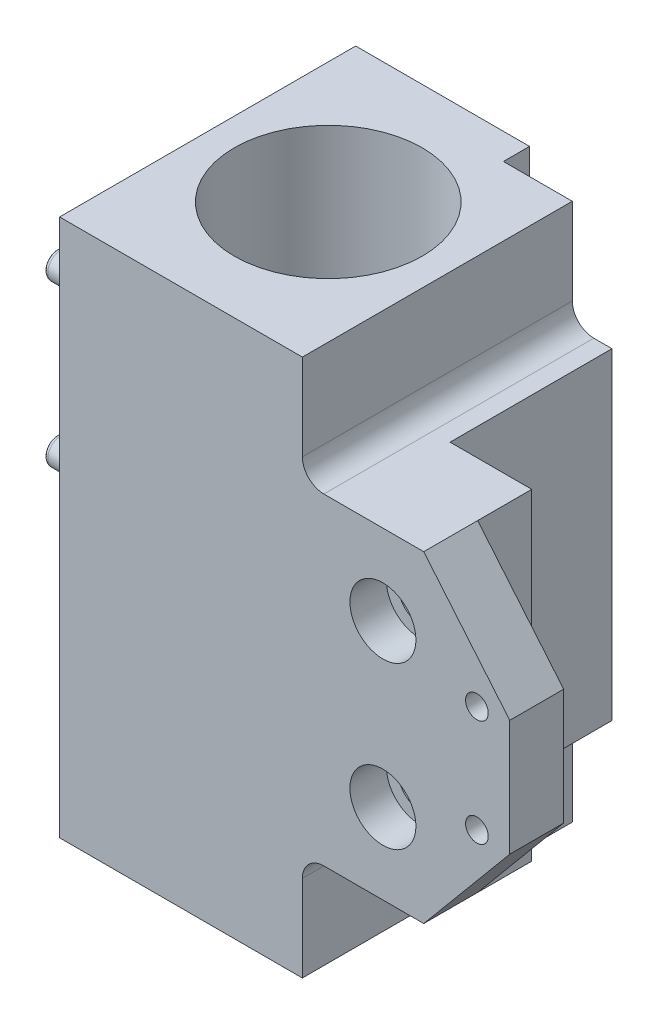
SolidWorks part; units mm, degrees
material "1060 Alloy"
ref_plane "Front Plane" through (0, 0, 0) normal (0, 0, 1) x (1, 0, 0)
ref_plane "Top Plane" through (0, 0, 0) normal (0, 1, 0) x (1, 0, 0)
ref_plane "Right Plane" through (0, 0, 0) normal (1, 0, 0) x (0, 0, -1)
sketch "Sketch1" plane through (0, 0, 0) normal (0, 1, 0) x (1, 0, 0)
  line L0 (-14.34, 17.58) -> (-14.34, -17.4)
  line L1 (-14.34, -17.4) -> (38.84, -17.4)
  line L2 (38.84, -17.4) -> (38.84, -11.03)
  line L3 (38.84, -11.03) -> (28.68, -11.03)
  line L4 (28.68, -11.03) -> (28.68, -4.64)
  line L5 (28.68, -4.64) -> (19.03, -4.64)
  line L6 (14.34, -4.64) -> (14.34, 14.49) construction
  line L7 (14.34, 14.49) -> (6.2, 14.49)
  line L8 (6.2, 14.49) -> (6.2, 17.58)
  line L9 (6.2, 17.58) -> (-14.34, 17.58)
  line L10 (0, 0) -> (0, 51.3699) construction
  line L11 (0, -11.1) -> (-14.34, -11.1) construction
  line L12 (14.34, 14.49) -> (19.03, 14.49)
  line L13 (19.03, 14.49) -> (19.03, -4.64)
  line L14 (14.34, -4.64) -> (19.03, -4.64) construction
  circle A0 centre (0, 0) radius 11.1
  dimension "D1" = 22.2
  dimension "D2" = 28.68
  dimension "D3" = 20.54
  dimension "D4" = 53.18
  dimension "D5" = 43.02
  dimension "D6" = 6.3
  dimension "D7" = 34.98
  dimension "D8" = 31.89
  dimension "D9" = 12.76
  dimension "D10" = 6.37
  dimension "D11" = 33.37
extrude "Boss-Extrude1" add sketch "Sketch1" along normal blind 31.765 and the other way blind 31.765
sketch "Sketch2" plane through (-14.34, 0, 0) normal (-1, 0, 0) x (0, 0, 1)
  line L0 (0, 0) -> (18.9221, 0) construction
  line L1 (-6.365, -19.06) -> (6.365, -19.06)
  line L2 (-6.365, -19.06) -> (-6.365, 19.06)
  line L3 (-6.365, 19.06) -> (6.365, 19.06)
  line L4 (6.365, -19.06) -> (6.365, 19.06)
  line L5 (0, 0) -> (0, -42.4085) construction
  dimension "D1" = 38.12
  dimension "D2" = 12.73
extrude "Boss-Extrude2" add sketch "Sketch2" along normal blind 9.43
sketch "Sketch3" plane through (0, 0, -17.58) normal (0, 0, -1) x (-1, 0, 0)
  line L0 (0, 0) -> (-38.84, 0) construction
  line L1 (-38.84, -31.765) -> (-38.84, 31.765) construction
  line L2 (-38.84, 6.85) -> (-28.68, 19.025)
  line L3 (-28.68, 19.025) -> (-16.88, 19.025)
  line L4 (-14.34, 21.565) -> (-14.34, 31.765)
  line L5 (-38.84, 6.85) -> (-38.84, 31.765)
  line L6 (-38.84, 31.765) -> (-14.34, 31.765)
  line L7 (-28.68, -19.025) -> (-16.88, -19.025)
  line L8 (-38.84, -31.765) -> (-14.34, -31.765)
  line L9 (-38.84, -6.85) -> (-38.84, -31.765)
  line L10 (-14.34, -21.565) -> (-14.34, -31.765)
  line L11 (-38.84, -6.85) -> (-28.68, -19.025)
  line L12 (-38.84, -6.85) -> (-38.84, 6.85) construction
  line L13 (-38.84, 31.765) -> (-28.68, 31.765) construction
  line L14 (-14.34, 21.565) -> (-14.34, -21.565) construction
  line L15 (-28.68, -31.765) -> (-28.68, 31.765) construction
  arc A0 (-16.88, 19.025) -> (-14.34, 21.565) centre (-16.88, 21.565) ccw
  arc A1 (-16.88, -19.025) -> (-14.34, -21.565) centre (-16.88, -21.565) cw
  dimension "D1" = 2.54
  dimension "D2" = 38.05
  dimension "D3" = 13.7
extrude "Cut-Extrude1" cut sketch "Sketch3" against normal through all
chamfer "Chamfer1" distance 1.6 angle 45 1 edges at (-23.77, -19.06, 0)
sketch "Sketch4" plane through (0, 0, -14.49) normal (0, 0, -1) x (-1, 0, 0)
  line L0 (0, 0) -> (-12.48, 0) construction
  line L1 (-13.89, 0) -> (-13.89, 7.9644) construction
  line L2 (-19.03, -19.025) -> (-19.03, 19.025) construction
  circle A0 centre (-12.48, 0) radius 1.41
  dimension "D1" = 2.82
  dimension "D2" = 5.14
extrude "Cut-Extrude2" cut sketch "Sketch4" against normal blind 11
sketch "Sketch5" plane through (0, 0, 4.64) normal (0, 0, -1) x (-1, 0, 0)
  line L0 (-23.855, -19.025) -> (-23.855, 19.025) construction
  line L1 (-19.03, -19.025) -> (-28.68, -19.025) construction
  line L2 (-28.68, 19.025) -> (-19.03, 19.025) construction
  line L3 (0, 0) -> (-49.0842, 0) construction
  line L4 (-23.855, 7.085) -> (-31.0346, 7.085) construction
  line L5 (-23.855, -7.085) -> (-34.1674, -7.085) construction
  circle A0 centre (-23.855, -9.53) radius 2.445
  circle A1 centre (-23.855, 9.53) radius 2.445
  dimension "D1" = 4.89
  dimension "D2" = 14.17
extrude "Cut-Extrude3" cut sketch "Sketch5" against normal through all
sketch "Sketch6" plane through (0, 0, 17.4) normal (0, 0, 1) x (1, 0, 0)
  circle A0 centre (23.855, -9.53) radius 3.9
  circle A1 centre (23.855, 9.53) radius 3.9
  dimension "D1" = 7.8
extrude "Cut-Extrude4" cut sketch "Sketch6" against normal blind 4.32
sketch "Sketch7" plane through (0, 0, 11.03) normal (0, 0, -1) x (-1, 0, 0)
  line L0 (0, 0) -> (-34.96, 0) construction
  line L1 (-34.96, 6.31) -> (-34.96, -6.31) construction
  line L2 (-34.96, 4.97) -> (-40.9332, 4.97) construction
  line L3 (-34.96, -4.97) -> (-40.9332, -4.97) construction
  line L4 (-36.3, 6.31) -> (-36.3, -6.31) construction
  line L5 (-38.84, -6.85) -> (-38.84, 6.85) construction
  circle A0 centre (-34.96, 6.31) radius 1.34
  circle A1 centre (-34.96, -6.31) radius 1.34
  dimension "D1" = 2.68
  dimension "D2" = 9.94
  dimension "D3" = 2.54
extrude "Cut-Extrude5" cut sketch "Sketch7" against normal through all
sketch "Sketch8" plane through (-23.77, 0, 0) normal (-1, 0, 0) x (0, 0, 1)
  circle A0 centre (0, 0) radius 2
  dimension "D1" = 4
extrude "Cut-Extrude6" cut sketch "Sketch8" against normal blind 10.5
sketch "Sketch9" plane through (-23.77, 0, 0) normal (-1, 0, 0) x (0, 0, 1)
  line L0 (0, -9.505) -> (0, 9.505) construction
  line L1 (0, 0) -> (-13.2131, 0) construction
  line L2 (0, -11.075) -> (2.7693, -11.075) construction
  line L3 (0, 11.075) -> (2.7693, 11.075) construction
  circle A0 centre (0, -9.505) radius 1.57
  circle A1 centre (0, 9.505) radius 1.57
  dimension "D2" = 3.14
  dimension "D1" = 22.15
extrude "Boss-Extrude3" add sketch "Sketch9" along normal blind 8.3
fillet "Fillet1" radius 0.5 2 edges at (-32.07, 9.505, 1.57) (-32.07, -9.505, 1.57)
